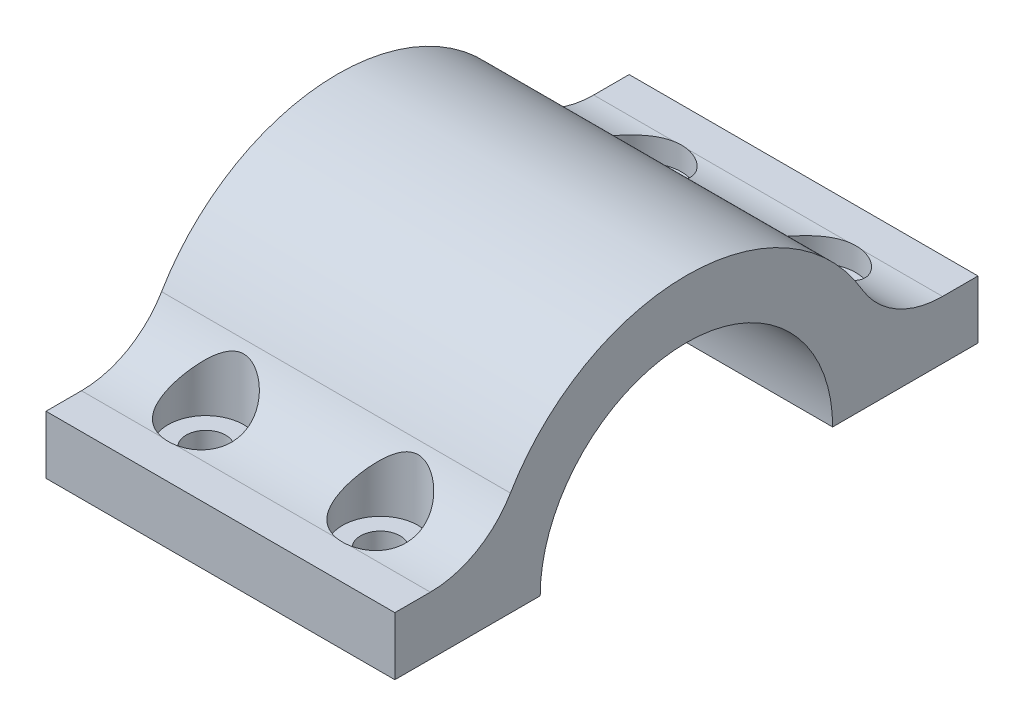
SolidWorks part; units mm, degrees
material "ABS"
ref_plane "Front Plane" through (0, 0, 0) normal (0, 0, 1) x (1, 0, 0)
ref_plane "Top Plane" through (0, 0, 0) normal (0, 1, 0) x (1, 0, 0)
ref_plane "Right Plane" through (0, 0, 0) normal (1, 0, 0) x (0, 0, -1)
sketch "Sketch1" plane through (0, 0, 0) normal (1, 0, 0) x (0, 0, -1)
  line L0 (-12.575, 0) -> (-25.075, 0)
  line L1 (-25.075, 0) -> (-25.075, 5)
  line L2 (-25.075, 5) -> (-16.8488, 5)
  line L3 (16.8488, 5) -> (25.075, 5)
  line L4 (25.075, 5) -> (25.075, 0)
  line L5 (25.075, 0) -> (12.575, 0)
  arc A0 (12.575, 0) -> (-12.575, 0) centre (0, 0) ccw
  arc A2 (-16.8488, 5) -> (16.8488, 5) centre (0, 0) cw
  dimension "D2" = 25.15
  dimension "D4" = 5
  dimension "D1" = 5
  dimension "D3" = 12.5
  dimension "D5" = 8.2262
extrude "Boss-Extrude1" add sketch "Sketch1" along normal mid plane 30
sketch "Sketch3" plane through (0, 0, 0) normal (0, -1, 0) x (1, 0, 0)
  line L0 (-15, 18.825) -> (-7.5, 18.825) construction
  line L1 (-15, 25.075) -> (-15, 12.575) construction
  line L2 (-7.5, 18.825) -> (0, 18.825) construction
  line L3 (0, 18.825) -> (7.5, 18.825) construction
  line L4 (7.5, 18.825) -> (15, 18.825) construction
  line L5 (15, 25.075) -> (15, 12.575) construction
  point P10 (-7.5, 18.825)
  point P11 (7.5, 18.825)
  dimension "D1" = 15
hole_wizard "CBORE for M3 SHCS1" positions "Sketch3" profile "Sketch4" counterbore size "M3" standard "ANSI Metric" end condition through all
sketch "Sketch4" plane through (7.5, 0, 18.825) normal (1, 0, 0) x (0, 0, -1)
  line L0 (0, 0) -> (0, 17.575)
  line L1 (0, 17.575) -> (3.25, 17.575)
  line L3 (3.25, 17.575) -> (3.25, 3)
  line L4 (3.25, 3) -> (1.7, 3)
  line L5 (1.7, 3) -> (1.7, 0)
  line L7 (1.7, 0) -> (0, 0)
  line L11 (0, -6.35) -> (0, 107.95) construction
  dimension "Thru Hole Dia." = 6.5
  dimension "Thru Hole Depth" = 17.575
  dimension "C'Bore Dia." = 3.4
  dimension "C'Bore Depth" = 3
mirror "Mirror1" about plane through (0, 0, 0) normal (0, 0, 1) of "CBORE for M3 SHCS1"
fillet "Fillet1" radius 8 6 edges at (-12.5401, 5, -16.8488) (-12.5401, 5, 16.8488) (12.5401, 5, -16.8488) (0, 5, -16.8488) (12.5401, 5, 16.8488) (0, 5, 16.8488)
equation "\"spar_diameter\"= 20mm"
